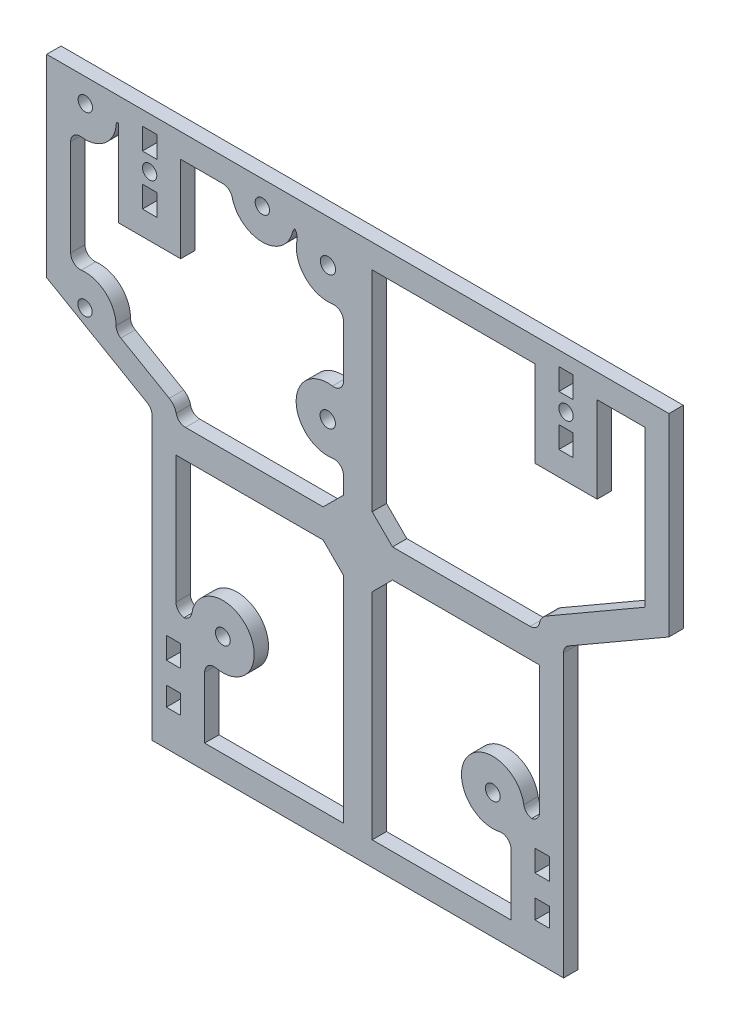
SolidWorks part; units mm, degrees
ref_plane "Alzado" through (0, 0, 0) normal (0, 0, 1) x (1, 0, 0)
ref_plane "Planta" through (0, 0, 0) normal (0, 1, 0) x (1, 0, 0)
ref_plane "Vista lateral" through (0, 0, 0) normal (1, 0, 0) x (0, 0, -1)
sketch "Croquis1" plane through (0, 0, 0) normal (0, 0, 1) x (1, 0, 0)
  line L65 (-65, 56.0095) -> (65, 56.0095)
  line L66 (-65, 56.0095) -> (-65, -57.1196)
  line L67 (-65, -57.1196) -> (65, -57.1196)
  line L68 (65, 56.0095) -> (65, -57.1196)
  point P4 (-45, 50.7595)
  line B0 (40, -47.1196) -> (40, -45.6196)
  line B1 (40, -45.6196) -> (37, -45.6196)
  line B2 (37, -45.6196) -> (37, -47.1196)
  line B3 (37, -47.1196) -> (40, -47.1196)
  line B4 (-37, -47.1196) -> (-37, -45.6196)
  line B5 (-37, -45.6196) -> (-40, -45.6196)
  line B6 (-40, -45.6196) -> (-40, -47.1196)
  line B7 (-40, -47.1196) -> (-37, -47.1196)
  line B8 (40, -41.1196) -> (40, -36.6196)
  line B9 (40, -36.6196) -> (37, -36.6196)
  line B10 (37, -36.6196) -> (37, -41.1196)
  line B11 (37, -41.1196) -> (40, -41.1196)
  line B12 (-37, -41.1196) -> (-37, -36.6196)
  line B13 (-37, -36.6196) -> (-40, -36.6196)
  line B14 (-40, -36.6196) -> (-40, -41.1196)
  line B15 (-40, -41.1196) -> (-37, -41.1196)
  line B16 (45, 38.0095) -> (45, 42.5095)
  line B17 (45, 42.5095) -> (42, 42.5095)
  line B18 (42, 42.5095) -> (42, 38.0095)
  line B19 (42, 38.0095) -> (45, 38.0095)
  line B20 (42, 53.0095) -> (42, 48.5095)
  line B21 (42, 48.5095) -> (45, 48.5095)
  line B22 (45, 48.5095) -> (45, 53.0095)
  line B23 (45, 53.0095) -> (42, 53.0095)
  line B24 (-42, 38.0095) -> (-42, 42.5095)
  line B25 (-42, 42.5095) -> (-45, 42.5095)
  line B26 (-45, 42.5095) -> (-45, 38.0095)
  line B27 (-45, 38.0095) -> (-42, 38.0095)
  line B28 (-45, 53.0095) -> (-45, 48.5095)
  line B29 (-45, 48.5095) -> (-42, 48.5095)
  line B30 (-42, 48.5095) -> (-42, 53.0095)
  line B31 (-42, 53.0095) -> (-45, 53.0095)
  line B32 (-45, 53.0095) -> (40, -47.1196) construction
  line B33 (-42, 53.0095) -> (42, 53.0095) construction
  line B34 (-40, -47.1196) -> (45, 53.0095) construction
  dimension "D1" = 3
  dimension "D2" = 20
  dimension "D3" = 20
  dimension "D4" = 10
sketch_block_instance "Bloque1-1"
sketch_block "Bloque1"
extrude "Saliente-Extruir1" add sketch "Croquis1" along normal blind 3
sketch "Croquis2" plane through (0, 0, 0) normal (0, 0, 1) x (1, 0, 0)
  line L0 (-43, -57.1196) -> (-43, 2.8804)
  line L1 (-65, -57.1196) -> (65, -57.1196) construction
  line L2 (-43, 2.8804) -> (-65, 15.5821)
  line L3 (-65, 56.0095) -> (-65, -57.1196) construction
  line L4 (-65, 15.5821) -> (-65, -57.1196)
  line L5 (-65, -57.1196) -> (-43, -57.1196)
  line L6 (-40, -36.6196) -> (-40, -41.1196) construction
  dimension "D1" = 3
  dimension "D2" = 60
  dimension "D3" = 60
extrude "Cortar-Extruir1" cut sketch "Croquis2" along normal blind 3
mirror "Simetría1" about plane through (0, 0, 0) normal (1, 0, 0) of "Cortar-Extruir1"
sketch "Croquis6" plane through (0, 0, 0) normal (0, 0, 1) x (1, 0, 0)
  point P1 (0, -30.9434)
  line B0 (65.4167, 22.0929) -> (50.1167, 22.118)
  line B1 (50.1167, 22.118) -> (50.0986, 11.118)
  line B2 (50.0986, 11.118) -> (65.3986, 11.0929)
  line B3 (65.3986, 11.0929) -> (65.4167, 22.0929)
  line B4 (47.5495, 42.1223) -> (47.5642, 51.0223)
  line B5 (47.5642, 51.0223) -> (59.7641, 51.0022)
  line B6 (59.7641, 51.0022) -> (59.7679, 53.3022)
  line B7 (59.7679, 53.3022) -> (58.7696, 54.3039)
  line B8 (58.7696, 54.3039) -> (-6.2304, 54.4106)
  line B9 (-6.2304, 54.4106) -> (-6.2353, 51.4106)
  line B10 (-6.2353, 51.4106) -> (-8.8395, 48.8149)
  line B11 (-8.8395, 48.8149) -> (-8.8921, 16.8149)
  line B12 (-8.8921, 16.8149) -> (-6.2964, 14.2106)
  line B13 (-6.2964, 14.2106) -> (-6.3162, 2.1107)
  line B14 (-6.3162, 2.1107) -> (-5.3179, 1.109)
  line B15 (-5.3179, 1.109) -> (58.682, 1.0039)
  line B16 (58.682, 1.0039) -> (59.6837, 2.0023)
  line B17 (59.6837, 2.0023) -> (59.6978, 10.6023)
  line B18 (59.6978, 10.6023) -> (50.0978, 10.618)
  line B19 (49.5986, 11.1189) -> (49.6167, 22.1188)
  line B20 (50.1175, 22.618) -> (59.7175, 22.6023)
  line B21 (59.7175, 22.6023) -> (59.7495, 42.1022)
  line B22 (59.7495, 42.1022) -> (47.5495, 42.1223)
  line B23 (-5.0327, 52.9086) -> (-5.0368, 50.3686)
  line B24 (-5.0368, 50.3686) -> (10.2031, 50.3436)
  line B25 (10.2031, 50.3436) -> (10.2073, 52.8836)
  line B26 (10.2073, 52.8836) -> (-5.0327, 52.9086)
  line B27 (11.2073, 52.882) -> (11.2031, 50.342)
  line B28 (11.2031, 50.342) -> (31.5231, 50.3086)
  line B29 (31.5231, 50.3086) -> (31.5273, 52.8486)
  line B30 (31.5273, 52.8486) -> (11.2073, 52.882)
  line B31 (15.2035, 1.8353) -> (15.2077, 4.3753)
  line B32 (15.2077, 4.3753) -> (-5.1123, 4.4087)
  line B33 (-5.1123, 4.4087) -> (-5.1165, 1.8687)
  line B34 (-5.1165, 1.8687) -> (15.2035, 1.8353)
  line B35 (41.6035, 1.792) -> (41.6076, 4.332)
  line B36 (41.6076, 4.332) -> (16.2077, 4.3737)
  line B37 (16.2077, 4.3737) -> (16.2035, 1.8337)
  line B38 (16.2035, 1.8337) -> (41.6035, 1.792)
  line B39 (47.5637, 50.7723) -> (47.55, 42.3723)
  line B40 (47.55, 42.3723) -> (58.1499, 42.3549)
  line B41 (58.1637, 50.7548) -> (58.1499, 42.3549)
  line B42 (58.1637, 50.7548) -> (47.5637, 50.7723)
  line B43 (61.5641, 50.9993) -> (58.1641, 51.0048)
  line B44 (58.1641, 51.0048) -> (58.1495, 42.1049)
  line B45 (58.1495, 42.1049) -> (61.5495, 42.0993)
  line B46 (61.5495, 42.0993) -> (61.5641, 50.9993)
  line B47 (30.8339, 32.5997) -> (30.8462, 40.0997)
  line B48 (30.8462, 40.0997) -> (-4.6038, 40.1579)
  line B49 (-4.6038, 40.1579) -> (-4.6161, 32.6579)
  line B50 (-4.6161, 32.6579) -> (30.8339, 32.5997)
  circle B51 centre (44.487, 4.0272) radius 1.6
  arc B52 (49.5986, 11.1189) -> (50.0978, 10.618) centre (50.0986, 11.118) ccw
  arc B53 (50.1175, 22.618) -> (49.6167, 22.1188) centre (50.1167, 22.118) ccw
  circle B54 centre (-6.288, 19.3106) radius 1.6
  circle B55 centre (45.6655, 51.8254) radius 1.6
  circle B56 centre (-6.2422, 47.2106) radius 1.6
  line B57 (59.6822, 1.0023) -> (59.7697, 54.3022) construction
  line B58 (59.6822, 1.0023) -> (-8.9179, 1.1149) construction
  line B59 (-8.9179, 1.1149) -> (-8.8303, 54.4149) construction
  line B60 (59.7697, 54.3022) -> (-8.8303, 54.4149) construction
  line B61 (-8.9179, 1.1149) -> (59.7697, 54.3022) construction
  line B62 (-27.3662, 12.2952) -> (-25.4262, 12.2921)
  line B63 (-24.8262, 12.2911) -> (-22.8862, 12.2879)
  line B64 (-22.5857, 12.5874) -> (-22.5826, 14.5274)
  line B65 (-22.5816, 15.1274) -> (-22.5784, 17.0674)
  line B66 (-22.8779, 17.3679) -> (-24.8179, 17.3711)
  line B67 (-25.1184, 17.0716) -> (-25.1216, 15.1316)
  line B68 (-25.4221, 14.8321) -> (-27.3621, 14.8352)
  line B69 (-27.9621, 14.8362) -> (-29.9021, 14.8394)
  line B70 (-30.5021, 14.8404) -> (-32.442, 14.8436)
  line B71 (-33.042, 14.8446) -> (-34.982, 14.8478)
  line B72 (-35.2816, 15.1482) -> (-35.2784, 17.0882)
  line B73 (-35.5779, 17.3887) -> (-37.5179, 17.3919)
  line B74 (-37.8184, 17.0924) -> (-37.8215, 15.1524)
  line B75 (-37.8225, 14.5524) -> (-37.8257, 12.6124)
  line B76 (-37.5262, 12.3119) -> (-35.5862, 12.3087)
  line B77 (-34.9862, 12.3078) -> (-33.0462, 12.3046)
  line B78 (-32.4462, 12.3036) -> (-30.5062, 12.3004)
  line B79 (-29.9062, 12.2994) -> (-27.9662, 12.2962)
  line B80 (-19.1926, 20.5818) -> (-17.6926, 20.5794)
  line B81 (-17.6926, 20.5794) -> (-17.6762, 30.5794)
  line B82 (-17.6762, 30.5794) -> (-19.1762, 30.5818)
  line B83 (-19.1762, 30.5818) -> (-24.1762, 30.59)
  line B84 (-24.1926, 20.59) -> (-19.1926, 20.5818)
  line B85 (-25.1762, 30.5917) -> (-25.1926, 20.5917)
  line B86 (-25.1926, 20.5917) -> (-24.1926, 20.59)
  line B87 (-24.1762, 30.59) -> (-25.1762, 30.5917)
  line B88 (-53.3052, 12.9378) -> (-53.3077, 11.4378)
  line B89 (-53.3077, 11.4378) -> (-38.3077, 11.4132)
  line B90 (-38.3077, 11.4132) -> (-38.3052, 12.9132)
  line B91 (-38.3052, 12.9132) -> (-38.297, 17.9132)
  line B92 (-53.297, 17.9378) -> (-53.3052, 12.9378)
  line B93 (-38.2954, 18.9132) -> (-53.2954, 18.9378)
  line B94 (-53.2954, 18.9378) -> (-53.297, 17.9378)
  line B95 (-38.297, 17.9132) -> (-38.2954, 18.9132)
  line B96 (-52.7926, 20.637) -> (-51.7926, 20.6354)
  line B97 (-51.7926, 20.6354) -> (-51.7761, 30.6354)
  line B98 (-51.7761, 30.6354) -> (-52.7761, 30.637)
  line B99 (-57.7926, 20.6452) -> (-52.7926, 20.637)
  line B100 (-52.7761, 30.637) -> (-57.7761, 30.6452)
  line B101 (-59.2926, 20.6477) -> (-57.7926, 20.6452)
  line B102 (-57.7761, 30.6452) -> (-59.2761, 30.6477)
  line B103 (-59.2761, 30.6477) -> (-59.2926, 20.6477)
  line B104 (-16.937, 54.4282) -> (-59.937, 54.4988)
  line B105 (-59.937, 54.4988) -> (-60.0088, 10.7488)
  line B106 (-60.0088, 10.7488) -> (-17.0089, 10.6782)
  line B107 (-17.0089, 10.6782) -> (-16.937, 54.4282)
  line B108 (-40.8486, 47.4074) -> (-40.8373, 54.2674)
  line B109 (-40.8373, 54.2674) -> (-41.4373, 54.2684)
  line B110 (-41.4373, 54.2684) -> (-41.4505, 46.2684)
  line B111 (-41.4505, 46.2684) -> (-45.0505, 46.2743)
  line B112 (-45.0505, 46.2743) -> (-45.0373, 54.2743)
  line B113 (-45.0373, 54.2743) -> (-45.6373, 54.2753)
  line B114 (-45.6373, 54.2753) -> (-45.6475, 48.0753)
  line B115 (-45.6475, 48.0753) -> (-47.1225, 48.0777)
  line B116 (-47.1225, 48.0777) -> (-47.1241, 47.0777)
  line B117 (-47.1241, 47.0777) -> (-48.1241, 47.0794)
  line B118 (-48.1241, 47.0794) -> (-48.1225, 48.0794)
  line B119 (-48.1225, 48.0794) -> (-49.5975, 48.0818)
  line B120 (-49.5975, 48.0818) -> (-49.5873, 54.2818)
  line B121 (-49.5873, 54.2818) -> (-50.1873, 54.2828)
  line B122 (-50.1873, 54.2828) -> (-50.2136, 38.2828)
  line B123 (-50.2136, 38.2828) -> (-49.6136, 38.2818)
  line B124 (-49.6136, 38.2818) -> (-49.6018, 45.4818)
  line B125 (-49.6018, 45.4818) -> (-27.3018, 45.4452)
  line B126 (-27.3018, 45.4452) -> (-27.3136, 38.2452)
  line B127 (-27.3136, 38.2452) -> (-26.7136, 38.2442)
  line B128 (-26.7136, 38.2442) -> (-26.6873, 54.2442)
  line B129 (-26.6873, 54.2442) -> (-27.2873, 54.2452)
  line B130 (-27.2873, 54.2452) -> (-27.2975, 48.0452)
  line B131 (-27.2975, 48.0452) -> (-28.7725, 48.0476)
  line B132 (-28.7725, 48.0476) -> (-28.7742, 47.0476)
  line B133 (-28.7742, 47.0476) -> (-29.7742, 47.0492)
  line B134 (-29.7742, 47.0492) -> (-29.7725, 48.0492)
  line B135 (-29.7725, 48.0492) -> (-31.2475, 48.0517)
  line B136 (-31.2475, 48.0517) -> (-31.2373, 54.2517)
  line B137 (-31.2373, 54.2517) -> (-31.8373, 54.2526)
  line B138 (-31.8373, 54.2526) -> (-31.8505, 46.2527)
  line B139 (-31.8505, 46.2527) -> (-35.4505, 46.2586)
  line B140 (-35.4505, 46.2586) -> (-35.4373, 54.2586)
  line B141 (-35.4373, 54.2586) -> (-36.0373, 54.2595)
  line B142 (-36.0373, 54.2595) -> (-36.0486, 47.3995)
  line B143 (-36.0486, 47.3995) -> (-40.8486, 47.4074)
  circle B144 centre (-56.9425, 51.1189) radius 2.5
  circle B145 centre (-19.9426, 51.0581) radius 2.5
  circle B146 centre (-57.0033, 14.1189) radius 2.5
  circle B147 centre (-57.0033, 14.1189) radius 1.5
  circle B148 centre (-20.0033, 14.0582) radius 1.5
  circle B149 centre (-19.9426, 51.0581) radius 1.5
  circle B150 centre (-56.9425, 51.1189) radius 1.5
  arc B151 (-25.4262, 12.2921) -> (-25.1257, 12.5916) centre (-25.4257, 12.5921) ccw
  arc B152 (-25.1257, 12.5916) -> (-24.8262, 12.2911) centre (-24.8257, 12.5911) ccw
  arc B153 (-22.8862, 12.2879) -> (-22.5857, 12.5874) centre (-22.8857, 12.5879) ccw
  arc B154 (-22.5826, 14.5274) -> (-22.8821, 14.8279) centre (-22.8826, 14.5279) ccw
  arc B155 (-22.8821, 14.8279) -> (-22.5816, 15.1274) centre (-22.8816, 15.1279) ccw
  arc B156 (-22.5784, 17.0674) -> (-22.8779, 17.3679) centre (-22.8784, 17.0679) ccw
  arc B157 (-24.8179, 17.3711) -> (-25.1184, 17.0716) centre (-24.8184, 17.0711) ccw
  arc B158 (-25.1216, 15.1316) -> (-24.8221, 14.8311) centre (-24.8216, 15.1311) ccw
  arc B159 (-24.8221, 14.8311) -> (-25.1226, 14.5316) centre (-24.8226, 14.5311) ccw
  arc B160 (-25.1226, 14.5316) -> (-25.4221, 14.8321) centre (-25.4226, 14.5321) ccw
  arc B161 (-27.3621, 14.8352) -> (-27.6625, 14.5357) centre (-27.3625, 14.5352) ccw
  arc B162 (-27.6625, 14.5357) -> (-27.9621, 14.8362) centre (-27.9625, 14.5362) ccw
  arc B163 (-29.9021, 14.8394) -> (-30.2025, 14.5399) centre (-29.9025, 14.5394) ccw
  arc B164 (-30.2025, 14.5399) -> (-30.5021, 14.8404) centre (-30.5025, 14.5404) ccw
  arc B165 (-32.442, 14.8436) -> (-32.7425, 14.5441) centre (-32.4425, 14.5436) ccw
  arc B166 (-32.7425, 14.5441) -> (-33.042, 14.8446) centre (-33.0425, 14.5446) ccw
  arc B167 (-34.982, 14.8478) -> (-35.2825, 14.5482) centre (-34.9825, 14.5478) ccw
  arc B168 (-35.2825, 14.5482) -> (-35.582, 14.8487) centre (-35.5825, 14.5487) ccw
  arc B169 (-35.582, 14.8487) -> (-35.2816, 15.1482) centre (-35.5816, 15.1487) ccw
  arc B170 (-35.2784, 17.0882) -> (-35.5779, 17.3887) centre (-35.5784, 17.0887) ccw
  arc B171 (-37.5179, 17.3919) -> (-37.8184, 17.0924) centre (-37.5184, 17.0919) ccw
  arc B172 (-37.8215, 15.1524) -> (-37.522, 14.8519) centre (-37.5216, 15.1519) ccw
  arc B173 (-37.522, 14.8519) -> (-37.8225, 14.5524) centre (-37.5225, 14.5519) ccw
  arc B174 (-37.8257, 12.6124) -> (-37.5262, 12.3119) centre (-37.5257, 12.6119) ccw
  arc B175 (-35.5862, 12.3087) -> (-35.2857, 12.6082) centre (-35.5857, 12.6087) ccw
  arc B176 (-35.2857, 12.6082) -> (-34.9862, 12.3078) centre (-34.9857, 12.6078) ccw
  arc B177 (-33.0462, 12.3046) -> (-32.7457, 12.6041) centre (-33.0457, 12.6046) ccw
  arc B178 (-32.7457, 12.6041) -> (-32.4462, 12.3036) centre (-32.4457, 12.6036) ccw
  arc B179 (-30.5062, 12.3004) -> (-30.2057, 12.5999) centre (-30.5057, 12.6004) ccw
  arc B180 (-30.2057, 12.5999) -> (-29.9062, 12.2994) centre (-29.9057, 12.5994) ccw
  arc B181 (-27.9662, 12.2962) -> (-27.6657, 12.5957) centre (-27.9657, 12.5962) ccw
  arc B182 (-27.6657, 12.5957) -> (-27.3662, 12.2952) centre (-27.3657, 12.5952) ccw
  line B183 (-59.937, 54.4988) -> (-17.0089, 10.6782) construction
  line B184 (-38.6, -50.8434) -> (38.6, -11.0434) construction
  line B185 (34.8, -35.5934) -> (-34.8, -35.5934)
  line B186 (-34.8, -26.2934) -> (34.8, -26.2934)
  line B187 (34.8, -16.8934) -> (-34.8, -16.8934)
  line B188 (-38.6, -50.8434) -> (38.6, -50.8434)
  circle B189 centre (28.2, -30.9434) radius 1.55
  circle B190 centre (-28.2, -30.9434) radius 1.55
sketch_block_instance "Bloque4-2"
sketch_block "Bloque4"
sketch_block_instance "Bloque6-1"
sketch_block "Bloque6"
sketch_block_instance "Bloque5-3"
sketch_block "Bloque5"
sketch "Croquis7" plane through (0, 0, 0) normal (0, 0, 1) x (1, 0, 0)
  circle A0 centre (-28.2, -30.9434) radius 1.55 construction
  circle A1 centre (28.2, -30.9434) radius 1.55 construction
  circle A2 centre (-6.2422, 47.2106) radius 1.6 construction
  circle A3 centre (-6.288, 19.3106) radius 1.6 construction
  circle A4 centre (-57.0033, 14.1189) radius 1.5 construction
  circle A5 centre (-19.9426, 51.0581) radius 1.5 construction
  circle A6 centre (-56.9425, 51.1189) radius 1.5 construction
  circle A7 centre (-28.2, -30.9434) radius 1.55
  circle A8 centre (28.2, -30.9434) radius 1.55
  circle A9 centre (-6.2422, 47.2106) radius 1.6
  circle A10 centre (-6.288, 19.3106) radius 1.6
  circle A11 centre (-57.0033, 14.1189) radius 1.5
  circle A12 centre (-19.9426, 51.0581) radius 1.5
  circle A13 centre (-56.9425, 51.1189) radius 1.5
extrude "Cortar-Extruir3" cut sketch "Croquis7" along normal blind 10
sketch "Croquis8" plane through (0, 0, 0) normal (0, 0, 1) x (1, 0, 0)
  line L4 (37, 51.0095) -> (3, 51.0095)
  line L5 (-26.4424, 51.0095) -> (-37, 51.0095)
  line L6 (-50, 51.0095) -> (-50.4434, 51.0095)
  line L7 (-11.6392, 51.0095) -> (-13.4427, 51.0095)
  line L12 (0, 0) -> (0, 59.3841) construction
  line L15 (0, 0) -> (57.482, 0) construction
  line L22 (0, 0) -> (-55.9879, 0) construction
  line L23 (3, 3) -> (3, 51.0095)
  line L28 (-3, 3) -> (-38, 3)
  line L29 (0, 0) -> (0, -63.1618) construction
  line L30 (-3, -3) -> (-3, -52.1196)
  line L31 (3, -3) -> (38, -3)
  line L36 (-3, 3) -> (-3, 13.588)
  line L37 (-3, -3) -> (-38, -3)
  line L38 (3, -3) -> (3, -52.1196)
  line L39 (3, 3) -> (38, 3)
  line L44 (0, 3) -> (-55.9879, 3) construction
  line L45 (-3, 0) -> (-3, 59.3841) construction
  line L46 (-3, 0) -> (-3, -63.1618) construction
  line L47 (0, -3) -> (-55.9879, -3) construction
  line L52 (0, -3) -> (57.482, -3) construction
  line L53 (3, 0) -> (3, -63.1618) construction
  line L54 (3, 0) -> (3, 59.3841) construction
  line L55 (0, 3) -> (57.482, 3) construction
  line L60 (-3, 25.0333) -> (-3, 41.4618)
  line L61 (3, -52.1196) -> (32, -52.1196)
  line L62 (-38, -3) -> (-38, -31.6196)
  line L63 (-3, 7.2426) -> (-7.2426, 3)
  line L68 (-7.2426, 3) -> (-7.2426, -3)
  line L69 (-7.2426, -3) -> (-3, -7.2426)
  line L70 (-3, -7.2426) -> (3, -7.2426)
  line L71 (3, -7.2426) -> (7.2426, -3)
  line L76 (7.2426, -3) -> (7.2426, 3)
  line L77 (7.2426, 3) -> (3, 7.2426)
  line L78 (3, 7.2426) -> (-3, 7.2426)
  line L79 (38, 3) -> (38, 5.7672)
  line L88 (37, 51.0095) -> (37, 33.0095)
  line L89 (37, 33.0095) -> (50, 33.0095)
  line L90 (50, 33.0095) -> (50, 51.0095)
  line L96 (-37, 33.0095) -> (-37, 51.0095)
  line L98 (-50, 51.0095) -> (-50, 33.0095)
  line L99 (-50, 33.0095) -> (-37, 33.0095)
  line L104 (-32, -52.1196) -> (-32, -36.2785)
  line L105 (-34.715, -31.6196) -> (-38, -31.6196)
  line L119 (32, -36.2785) -> (32, -52.1196)
  line L120 (-60, 45.3829) -> (-60, 19.8869)
  line L121 (-50.5937, 13.0382) -> (-38, 5.7672)
  line L122 (-38, 5.7672) -> (-38, 3)
  line L123 (-32, -52.1196) -> (-3, -52.1196)
  line L125 (38, 5.7672) -> (60, 18.4689)
  line L126 (60, 18.4689) -> (60, 51.0095)
  line L127 (60, 51.0095) -> (50, 51.0095)
  line L157 (38, -31.6196) -> (34.715, -31.6196)
  line L159 (38, -31.6196) -> (38, -3)
  arc A0 (-60, 45.3829) -> (-50.4434, 51.0095) centre (-56.9425, 51.1189) ccw
  circle A3 centre (0, 0) radius 7.2426 construction
  arc A6 (-50.5937, 13.0382) -> (-60, 19.8869) centre (-57.0033, 14.1189) ccw
  arc A23 (-26.4424, 51.0095) -> (-13.4427, 51.0095) centre (-19.9426, 51.0581) ccw
  arc A24 (-11.6392, 51.0095) -> (-3, 41.4618) centre (-6.2422, 47.2106) ccw
  arc A27 (-3, 25.0333) -> (-3, 13.588) centre (-6.288, 19.3106) ccw
  arc A31 (-32, -36.2785) -> (-34.715, -31.6196) centre (-28.2, -30.9434) ccw
  arc A32 (34.715, -31.6196) -> (32, -36.2785) centre (28.2, -30.9434) ccw
  dimension "D3" = 6
  dimension "D1" = 3
  dimension "D2" = 3
extrude "Cortar-Extruir4" cut sketch "Croquis8" along normal blind 10 contours A27 L60 A24 L7 A23 L5 L96 L99 L98 L6 A0 L120 A6 L121 L28 L63 L36 | L125 L126 L127 L90 L89 L88 L4 L23 L77 L39 | A32 L157 L159 L31 L71 L38 L61 L119 | A31 L104 L123 L30 L69 L37 L122 L105 region at (28.6273, 27.1989, 0) region at (-29.8976, 25.6723, 0) region at (18.7403, -26.219, 0) region at (-18.7403, -26.219, 0)
sketch "Croquis9" plane through (0, 0, 0) normal (0, 0, 1) x (1, 0, 0)
  line L0 (40, -47.1196) -> (40, -45.6196) construction
  line L1 (-40, -45.6196) -> (-37, -45.6196)
  line L2 (-40, -45.6196) -> (-40, -49.6196)
  line L3 (-40, -49.6196) -> (-37, -49.6196)
  line L4 (-37, -45.6196) -> (-37, -49.6196)
  line L5 (37, -45.6196) -> (40, -45.6196)
  line L6 (37, -45.6196) -> (37, -49.6196)
  line L7 (37, -49.6196) -> (40, -49.6196)
  line L8 (40, -45.6196) -> (40, -49.6196)
  line L9 (-37, -47.1196) -> (-37, -45.6196) construction
  dimension "D1" = 4
extrude "Cortar-Extruir5" cut sketch "Croquis9" along normal blind 10
sketch "Croquis10" plane through (0, 0, 0) normal (0, 0, 1) x (1, 0, 0)
  line L0 (-45, 48.5095) -> (-42, 42.5095) construction
  line L2 (42, 42.5095) -> (45, 48.5095) construction
  circle A0 centre (43.5, 45.5095) radius 1.5
  circle A1 centre (-43.5, 45.5095) radius 1.5
  dimension "D1" = 3
extrude "Cortar-Extruir6" cut sketch "Croquis10" along normal through all both
fillet "Redondeo1" radius 2 19 edges at (32, -36.2785, 1.5) (38, -31.6196, 1.5) (34.715, -31.6196, 1.5) (-32, -36.2785, 1.5) (-38, -31.6196, 1.5) (-34.715, -31.6196, 1.5) (-43, 2.8804, 1.5) (43, 2.8804, 1.5) (38, 3, 1.5) (-38, 3, 1.5) (-3, 13.588, 1.5) (-3, 41.4618, 1.5) (-60, 45.3829, 1.5) (-26.4424, 51.0095, 1.5) (-13.4427, 51.0095, 1.5) (-11.6392, 51.0095, 1.5) (-3, 25.0333, 1.5) (-60, 19.8869, 1.5) (-50.5937, 13.0382, 1.5)
fillet "Redondeo2" radius 3 2 edges at (-38, 5.7672, 1.5) (38, 5.7672, 1.5)
